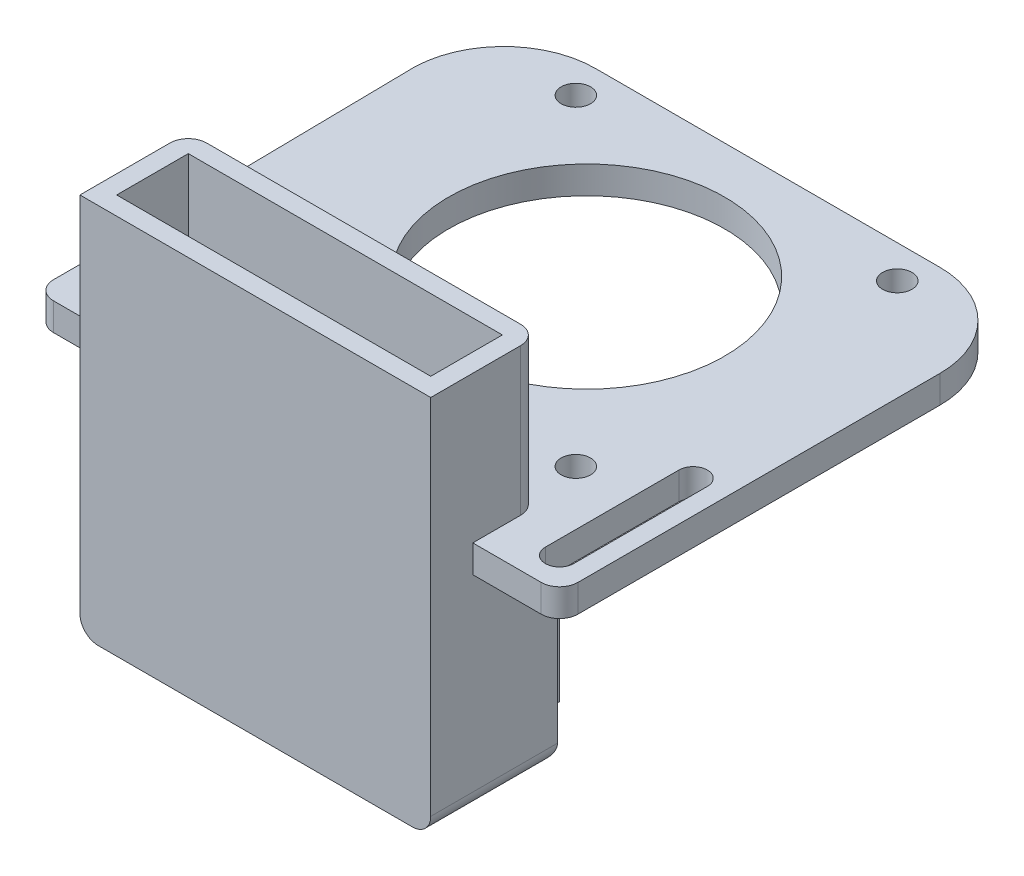
SolidWorks part; units mm, degrees
ref_plane "Alzado" through (0, 0, 0) normal (0, 0, 1) x (1, 0, 0)
ref_plane "Planta" through (0, 0, 0) normal (0, 1, 0) x (1, 0, 0)
ref_plane "Vista lateral" through (0, 0, 0) normal (1, 0, 0) x (0, 0, -1)
sketch "Croquis1" plane through (0, 0, 0) normal (0, 1, 0) x (1, 0, 0)
  line L0 (0, 19.0123) -> (0, -30.4096) construction
  line L1 (-17.6842, 17.4123) -> (-17.6842, -30.4096) construction
  line L2 (17.3158, -17.5877) -> (16.9891, -16.0214) construction
  line L3 (17.3158, -17.5877) -> (-29.1922, -17.5877) construction
  line L6 (-29.2494, 19.0123) -> (-29.2494, 21.0123)
  line L7 (-29.2494, 21.0123) -> (28.3658, 21.0123)
  line L8 (26.3658, -26.8596) -> (26.3658, -12.3158)
  line L11 (23.2658, -26.8596) -> (23.2658, -12.3158)
  line L12 (26.3658, -26.8596) -> (26.3658, -12.3158)
  line L13 (-28.734, -15.7212) -> (-29.2494, 19.0123)
  line L14 (-26.7342, -26.8596) -> (-26.7342, -12.3158)
  line L15 (-23.6342, -26.8596) -> (-23.6342, -12.3158)
  line L16 (-28.7342, -26.8596) -> (-28.7342, -30.4096)
  line L17 (-25.1842, -30.4096) -> (-28.7342, -30.4096)
  line L18 (-25.1842, -30.4096) -> (26.3658, -30.4096)
  line L19 (28.3658, -12.3158) -> (28.3658, 17.0123)
  line L20 (-28.734, -15.7212) -> (-28.7342, -26.8596)
  line L21 (28.3658, -12.3158) -> (28.3658, -30.4096)
  line L22 (26.3658, -30.4096) -> (28.3658, -30.4096)
  line L24 (28.3658, 17.0123) -> (28.3658, 19.0123)
  line L25 (28.3658, 19.0123) -> (28.3658, 21.0123)
  circle A0 centre (17.3158, 17.4123) radius 1.6
  circle A1 centre (-17.6842, 17.4123) radius 1.6
  circle A2 centre (17.3158, -17.5877) radius 1.6
  arc A3 (23.2658, -26.8596) -> (26.3658, -26.8596) centre (24.8158, -26.8596) ccw
  arc A4 (26.3658, -12.3158) -> (23.2658, -12.3158) centre (24.8158, -12.3158) ccw
  arc A5 (-26.7342, -26.8596) -> (-23.6342, -26.8596) centre (-25.1842, -26.8596) ccw
  arc A6 (-23.6342, -12.3158) -> (-26.7342, -12.3158) centre (-25.1842, -12.3158) ccw
  circle A7 centre (0, 0.9042) radius 15.0187
  circle A8 centre (-17.6842, -17.5877) radius 1.6
  point P7 (-0.1842, -19.5877)
  point P12 (24.8158, -19.5877)
  point P17 (-25.127, -17.5877)
  dimension "D3" = 50
  dimension "D6" = 2
  dimension "D1" = 35
  dimension "D2" = 35
  dimension "D4" = 3.1
  dimension "D5" = 3.1
  dimension "D7" = 3.6
  dimension "D8" = 3.6
  dimension "D9" = 35
extrude "Saliente-Extruir1" add sketch "Croquis1" along normal blind 3 contours L0 L13 L20 L16 L17 L18 A7 A6 L15 A5 L14 A1 | L0 A7 L18 L22 L21 L19 L24 A0 A2 A4 L8 A3 L11 region at (-12.5921, 0, 29.6374)
sketch "Croquis2" plane through (0, 0, 0) normal (0, -1, 0) x (1, 0, 0)
  line L0 (17.3158, 21.1877) -> (-19.2842, 21.1877) construction
  line L2 (-19.2842, 21.1877) -> (-19.2842, 37.9877) construction
  line L3 (18.9158, 21.1877) -> (-19.2842, 21.1877)
  line L4 (18.9158, 21.1877) -> (18.9158, 37.9877)
  line L5 (18.9158, 37.9877) -> (-19.2842, 37.9877)
  line L7 (-19.2842, 37.9877) -> (-19.2842, 21.1877)
  line L9 (18.9158, 21.1877) -> (18.9158, 31.9033) construction
  dimension "D1" = 16.8
extrude "Saliente-Extruir2" add sketch "Croquis2" along normal blind 40 and the other way blind 6
sketch "Croquis3" plane through (0, -40, 0) normal (0, -1, 0) x (1, 0, 0)
  line L12 (-17.2842, 35.9877) -> (-17.2842, 23.1877)
  line L13 (-17.2842, 35.9877) -> (-17.2842, 23.1877)
  line L16 (16.9158, 23.1877) -> (16.9158, 35.9877)
  line L17 (16.9158, 35.9877) -> (-17.2842, 35.9877)
  line L19 (-17.2842, 23.1877) -> (16.9158, 23.1877)
  line L20 (16.9158, 23.1877) -> (16.9158, 35.9877)
  line L21 (16.9158, 35.9877) -> (-17.2842, 35.9877)
  line L23 (-17.2842, 23.1877) -> (16.9158, 23.1877)
  dimension "D1" = 2
extrude "Cortar-Extruir1" cut sketch "Croquis3" against normal blind 40
sketch "Croquis5" plane through (0, 0, 21.1877) normal (0, 0, -1) x (-1, 0, 0)
  line L0 (-17.6158, 0) -> (-17.6158, -40) construction
  line L1 (-18.9158, 0) -> (19.2842, 0) construction
  line L2 (19.2842, -40) -> (-18.9158, -40) construction
  line L3 (-18.9158, 0) -> (-18.9158, -40) construction
  line L4 (-18.9158, -1.3) -> (20.3383, -1.3) construction
  line L5 (-16.6158, -2.3) -> (6.8842, -2.3)
  line L10 (6.8842, -2.3) -> (6.8842, -17)
  line L11 (-16.6158, -17) -> (6.8842, -17)
  line L12 (-16.6158, -2.3) -> (-16.6158, -17)
  dimension "D1" = 1.3
  dimension "D2" = 1.3
extrude "Cortar-Extruir2" cut sketch "Croquis5" against normal blind 2
sketch "Croquis7" plane through (0, 0, 21.1877) normal (0, 0, -1) x (-1, 0, 0)
  line L4 (6.8842, -2.3) -> (-16.6158, -2.3) construction
  line L5 (-16.6158, -2.3) -> (-16.6158, -17) construction
  line L6 (6.8842, -17) -> (6.8842, -2.3) construction
  line L7 (-16.6158, -17) -> (6.8842, -17) construction
  line L8 (7.8842, -18) -> (7.8842, -1.3)
  line L9 (-17.6158, -1.3) -> (-17.6158, -18)
  line L10 (7.8842, -1.3) -> (-17.6158, -1.3)
  line L11 (-17.6158, -18) -> (7.8842, -18)
  line L12 (7.8842, -18) -> (7.8842, -1.3)
  line L13 (-17.6158, -1.3) -> (-17.6158, -18)
  line L14 (7.8842, -1.3) -> (-17.6158, -1.3)
  line L15 (-17.6158, -18) -> (7.8842, -18)
  line L16 (6.8842, -2.3) -> (-16.6158, -2.3)
  line L17 (-16.6158, -2.3) -> (-16.6158, -17)
  line L18 (6.8842, -17) -> (6.8842, -2.3)
  line L19 (-16.6158, -17) -> (6.8842, -17)
  dimension "D1" = 1
extrude "Saliente-Extruir11" add sketch "Croquis7" along normal blind 1.5
sketch "Croquis8" plane through (0, -40, 0) normal (0, -1, 0) x (1, 0, 0)
  line L1 (18.9158, 21.1877) -> (-19.2842, 21.1877)
  line L2 (18.9158, 21.1877) -> (18.9158, 37.9877)
  line L3 (18.9158, 37.9877) -> (-19.2842, 37.9877)
  line L4 (-19.2842, 21.1877) -> (-19.2842, 37.9877)
extrude "Cortar-Extruir8" cut sketch "Croquis8" against normal blind 19.5
sketch "Croquis9" plane through (0, -20.5, 0) normal (0, -1, 0) x (1, 0, 0)
  line L0 (-19.2842, 37.9877) -> (-19.2842, 21.1877) construction
  line L1 (18.9158, 21.1877) -> (-19.2842, 21.1877)
  line L2 (18.9158, 21.1877) -> (18.9158, 37.9877)
  line L3 (18.9158, 37.9877) -> (-19.2842, 37.9877)
  line L4 (-19.2842, 21.1877) -> (-19.2842, 37.9877)
  line L5 (18.9158, 37.9877) -> (-19.2842, 37.9877) construction
extrude "Saliente-Extruir12" add sketch "Croquis9" along normal blind 2
sketch "Croquis11" plane through (0, 6, 0) normal (0, 1, 0) x (1, 0, 0)
  line L1 (-19.2842, -21.1877) -> (18.9158, -21.1877)
  line L2 (-19.2842, -21.1877) -> (-19.2842, -37.9877)
  line L3 (-19.2842, -37.9877) -> (18.9158, -37.9877)
  line L4 (18.9158, -21.1877) -> (18.9158, -37.9877)
extrude "Saliente-Extruir13" add sketch "Croquis11" along normal blind 13
sketch "Croquis12" plane through (0, 19, 0) normal (0, 1, 0) x (1, 0, 0)
  line L8 (-17.2842, -35.9877) -> (16.9158, -35.9877)
  line L9 (16.9158, -35.9877) -> (16.9158, -23.1877)
  line L10 (16.9158, -23.1877) -> (-17.2842, -23.1877)
  line L11 (-17.2842, -23.1877) -> (-17.2842, -35.9877)
  line L12 (-17.2842, -35.9877) -> (16.9158, -35.9877)
  line L13 (16.9158, -35.9877) -> (16.9158, -23.1877)
  line L14 (16.9158, -23.1877) -> (-17.2842, -23.1877)
  line L15 (-17.2842, -23.1877) -> (-17.2842, -35.9877)
  dimension "D1" = 2
extrude "Cortar-Extruir9" cut sketch "Croquis12" against normal blind 25
sketch "Croquis13" plane through (0, 0, 21.1877) normal (0, 0, -1) x (-1, 0, 0)
  line L1 (19.2842, 0) -> (13.7842, 0)
  line L2 (19.2842, 0) -> (19.2842, -5)
  line L3 (19.2842, -5) -> (13.7842, -5)
  line L4 (13.7842, 0) -> (13.7842, -5)
  dimension "D1" = 5.5
  dimension "D2" = 5
extrude "Saliente-Extruir14" add sketch "Croquis13" against normal blind 15
sketch "Croquis14" plane through (0, 0, 0) normal (0, 1, 0) x (1, 0, 0)
  line L1 (-13.7842, -35.9877) -> (-17.2842, -35.9877)
  line L2 (-13.7842, -35.9877) -> (-13.7842, -23.1877)
  line L3 (-13.7842, -23.1877) -> (-17.2842, -23.1877)
  line L4 (-17.2842, -35.9877) -> (-17.2842, -23.1877)
extrude "Saliente-Extruir15" add sketch "Croquis14" along normal blind 10 and the other way blind 14
sketch "Croquis16" plane through (-13.7842, 0, 0) normal (1, 0, 0) x (0, 0, -1)
  line L1 (-23.1877, -14) -> (-35.9877, -14)
  line L2 (-23.1877, -14) -> (-23.1877, 10)
  line L3 (-23.1877, 10) -> (-35.9877, 10)
  line L4 (-35.9877, -14) -> (-35.9877, 10)
extrude "Saliente-Extruir16" add sketch "Croquis16" along normal blind 2.5
sketch "Croquis19" plane through (0, 3, 0) normal (0, 1, 0) x (1, 0, 0)
  line L3 (28.3658, -30.4096) -> (28.3658, 21.0123) construction
  line L4 (-29.1441, 10.908) -> (-29.2494, 21.0123)
  line L5 (-29.2494, 21.0123) -> (-19.1446, 21.0123)
  line L6 (18.3658, 21.0123) -> (28.3658, 21.0123)
  line L7 (-28.7342, -28.4096) -> (-28.7342, -30.4096)
  line L8 (-28.7342, -30.4096) -> (-26.7342, -30.4096)
  line L9 (28.3658, -30.4096) -> (28.3658, -28.4096)
  line L10 (28.3658, 21.0123) -> (28.3658, 11.0123)
  line L13 (26.3658, -30.4096) -> (28.3658, -30.4096)
  line L14 (28.3658, -30.4096) -> (28.3658, -28.4096)
  arc A0 (18.3658, 21.0123) -> (28.3658, 11.0123) centre (18.3658, 11.0123) cw
  arc A1 (-19.1446, 21.0123) -> (-29.1441, 10.908) centre (-19.1446, 11.0123) ccw
  arc A2 (28.3658, -28.4096) -> (26.3658, -30.4096) centre (26.3658, -28.4096) cw
  arc A3 (-28.7342, -28.4096) -> (-26.7342, -30.4096) centre (-26.7342, -28.4096) ccw
  line M6 (18.9158, -30.4096) -> (28.3658, -30.4096)
  line M7 (28.3658, -30.4096) -> (28.3658, 21.0123)
  line M9 (-29.2494, 19.0123) -> (-28.734, -15.7212)
  line M39 (28.3658, 21.0123) -> (-29.2494, 21.0123)
  dimension "D1" = 10
  dimension "D2" = 2
extrude "Cortar-Extruir12" cut sketch "Croquis19" against normal blind 3 contours A0 M39 M7 | A1 L4 M39 M9 | A2 M7 M6 | A3 L8 L7 region at (27.9191, 3, 29.9629) region at (26.1321, 3, -18.7786) region at (-26.9633, 3, -18.7579)
sketch "Croquis20" plane through (-28.9609, 0, 0.4298) normal (-0.9999, 0, 0.0148) x (0.0148, 0, 0.9999)
  line L1 (-14.7211, 3) -> (-22.2869, 3)
  line L2 (-14.7211, 3) -> (-14.7211, -0.2178)
  line L3 (-14.7211, -0.2178) -> (-22.2869, -0.2178)
  line L4 (-22.2869, 3) -> (-22.2869, -0.2178)
extrude "Cortar-Extruir13" cut sketch "Croquis20" against normal blind 0.5
sketch "Croquis22" plane through (0, 10, 0) normal (0, 1, 0) x (1, 0, 0)
  line L1 (-17.2842, -23.1877) -> (-11.2842, -23.1877)
  line L2 (-17.2842, -23.1877) -> (-17.2842, -35.9877)
  line L3 (-17.2842, -35.9877) -> (-11.2842, -35.9877)
  line L4 (-11.2842, -23.1877) -> (-11.2842, -35.9877)
extrude "Cortar-Extruir14" cut sketch "Croquis22" against normal blind 27
sketch "Croquis23" plane through (0, 19, 0) normal (0, 1, 0) x (1, 0, 0)
  line L0 (16.9158, -35.9877) -> (16.9158, -23.1877) construction
  line L1 (-17.2842, -35.9877) -> (16.9158, -35.9877)
  line L2 (-17.2842, -35.9877) -> (-17.2842, -32.9877)
  line L3 (-17.2842, -32.9877) -> (16.9158, -32.9877)
  line L4 (16.9158, -35.9877) -> (16.9158, -32.9877)
  dimension "D1" = 3
extrude "Saliente-Extruir17" add sketch "Croquis23" against normal blind 40
fillet "Redondeo3" radius 10 1 edges at (-0.1842, -20.5, 32.9877)
sketch "Croquis24" plane through (0, 19, 0) normal (0, 1, 0) x (1, 0, 0)
  line L0 (16.9158, -32.9877) -> (16.9158, -23.1877) construction
  line L1 (-17.2842, -23.1877) -> (16.9158, -23.1877)
  line L2 (-17.2842, -23.1877) -> (-17.2842, -25.1877)
  line L3 (-17.2842, -25.1877) -> (16.9158, -25.1877)
  line L4 (16.9158, -23.1877) -> (16.9158, -25.1877)
  dimension "D1" = 2
extrude "Saliente-Extruir18" add sketch "Croquis24" against normal blind 21
sketch "Croquis25" plane through (0, 0, 21.1877) normal (0, 0, -1) x (-1, 0, 0)
  line L1 (19.2842, 3) -> (-18.9158, 3)
  line L2 (19.2842, 3) -> (19.2842, 19)
  line L3 (19.2842, 19) -> (-18.9158, 19)
  line L4 (-18.9158, 3) -> (-18.9158, 19)
extrude "Cortar-Extruir15" cut sketch "Croquis25" against normal blind 2
sketch "Croquis26" plane through (0, 0, 37.9877) normal (0, 0, 1) x (1, 0, 0)
  line L1 (-19.2842, 19) -> (18.9158, 19)
  line L2 (-19.2842, 19) -> (-19.2842, -22.5)
  line L3 (-19.2842, -22.5) -> (18.9158, -22.5)
  line L4 (18.9158, 19) -> (18.9158, -22.5)
extrude "Cortar-Extruir16" cut sketch "Croquis26" against normal blind 3
fillet "Redondeo4" radius 2 6 edges at (-19.2842, -11.25, 21.1877) (-19.2842, -22.5, 28.0877) (-0.1842, -22.5, 21.1877) (18.9158, -22.5, 28.0877) (-19.2842, 11, 23.1877) (18.9158, 11, 23.1877)
